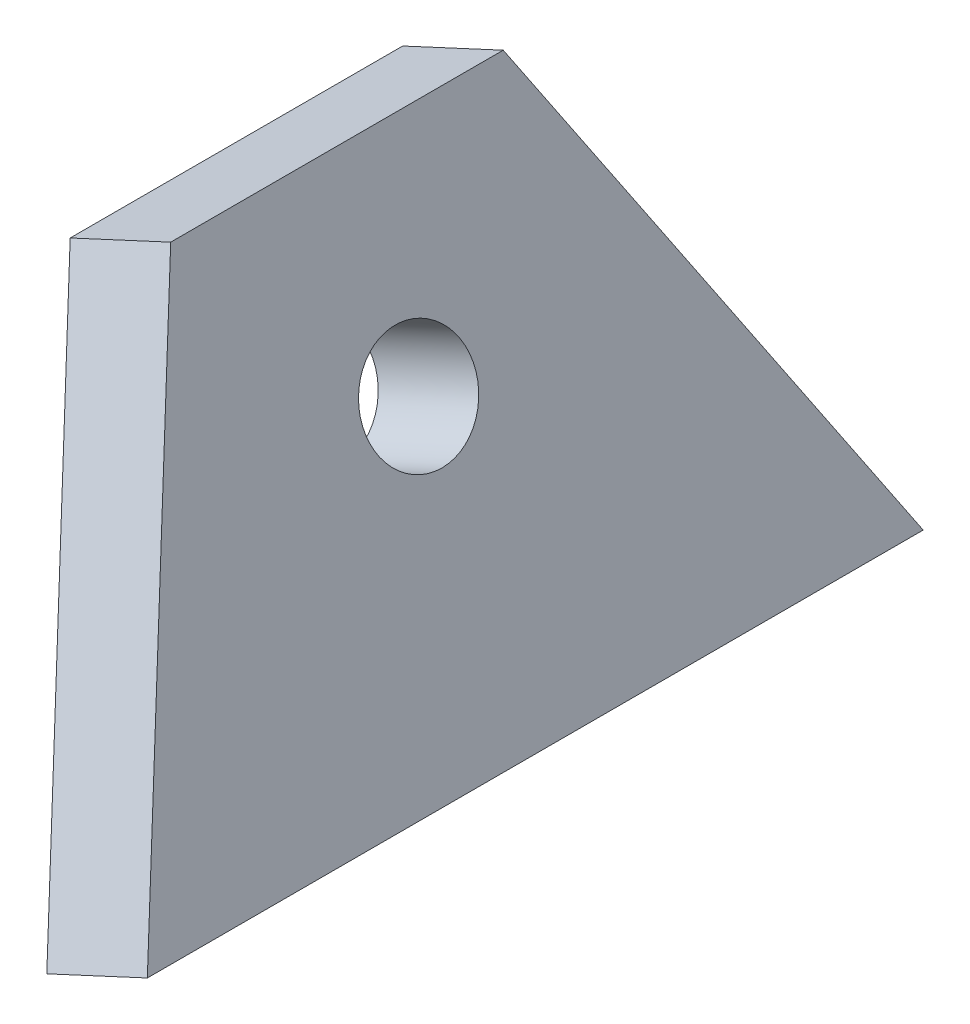
SolidWorks part; units mm, degrees
material "6061-T6 (SS)"
ref_plane "Alzado" through (0, 0, 0) normal (0, 0, 1) x (1, 0, 0)
ref_plane "Planta" through (0, 0, 0) normal (0, 1, 0) x (1, 0, 0)
ref_plane "Vista lateral" through (0, 0, 0) normal (1, 0, 0) x (0, 0, -1)
sketch3d "Sk_Plano_Yugo"
  point P0 (450.0041, 392.4955, 0)
  point P1 (450.0041, 392.4955, 10)
  point P2 (445.7944, 401.5663, 0)
ref_plane "Plano_Yugo" through (520.1314, 241.3899, 0) normal (-0.9071, -0.421, 0) x (0, 0, 1)
sketch "Sk_Yugo" plane through (520.1314, 241.3899, 0) normal (-0.9071, -0.421, 0) x (0, 0, 1)
  line L0 (-14, 229.5855) -> (14, 229.5855)
  line L1 (14, 229.5855) -> (6, 246.5855)
  line L2 (6, 246.5855) -> (-6, 246.5855)
  line L3 (-6, 246.5855) -> (-14, 229.5855)
extrude "Yugo" add sketch "Sk_Yugo" against normal blind 4
sketch3d "Sk_Ojo_cable"
  line L0 (418.3664, 458.2911, 0) -> (423.8088, 460.8169, 0)
  dimension "D1" = 6
sweep "Ojo_cable" cut path "Sk_Ojo_cable" circular profile diameter 4 parameters "D3"=4
